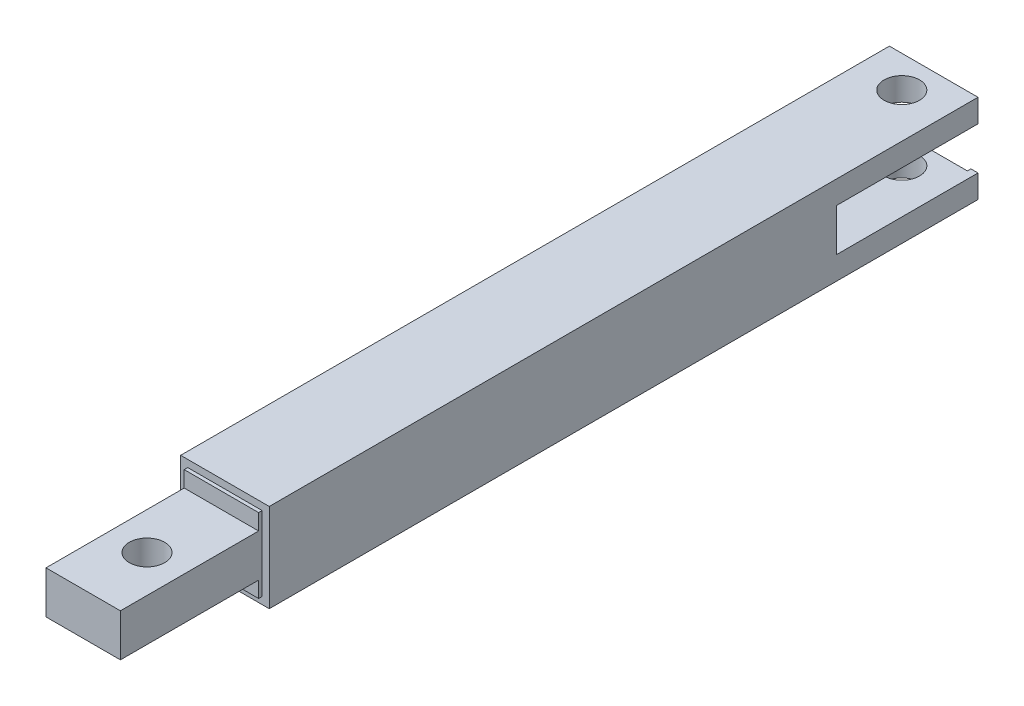
SolidWorks part; units mm, degrees
ref_plane "Front Plane" through (0, 0, 0) normal (0, 0, 1) x (1, 0, 0)
ref_plane "Top Plane" through (0, 0, 0) normal (0, 1, 0) x (1, 0, 0)
ref_plane "Right Plane" through (0, 0, 0) normal (1, 0, 0) x (0, 0, -1)
sketch "Sketch1" plane through (0, 0, 0) normal (0, 0, 1) x (1, 0, 0)
  line L0 (-10.5, 10.5) -> (10.5, 10.5)
  line L1 (-12.5, 12.5) -> (12.5, 12.5)
  line L2 (-12.5, 12.5) -> (-12.5, -12.5)
  line L3 (-12.5, -12.5) -> (12.5, -12.5)
  line L4 (12.5, 12.5) -> (12.5, -12.5)
  line L5 (-12.5, 12.5) -> (12.5, -12.5) construction
  line L6 (-12.5, -12.5) -> (12.5, 12.5) construction
  line L7 (10.5, 10.5) -> (10.5, -10.5)
  line L8 (-10.5, -10.5) -> (10.5, -10.5)
  line L9 (-10.5, 10.5) -> (-10.5, -10.5)
  point P0 (0, 0)
  dimension "D1" = 25
  dimension "D2" = 25
  dimension "D3" = 2
extrude "Boss-Extrude1" add sketch "Sketch1" along normal blind 200
sketch "Sketch2" plane through (12.5, 0, 0) normal (1, 0, 0) x (0, 0, -1)
  line L0 (0, -12.5) -> (0, 12.5) construction
  line L1 (0, -6) -> (-40, -6)
  line L2 (0, -6) -> (0, 6)
  line L3 (0, 6) -> (-40, 6)
  line L4 (-40, -6) -> (-40, 6)
  line L5 (-200, -12.5) -> (0, -12.5) construction
  dimension "D1" = 40
  dimension "D2" = 6.5
  dimension "D3" = 12
extrude "Cut-Extrude1" cut sketch "Sketch2" against normal through all
sketch "Sketch3" plane through (0, 12.5, 0) normal (0, 1, 0) x (1, 0, 0)
  line L0 (12.5, 0) -> (-12.5, 0) construction
  circle A0 centre (0, -9) radius 5
  dimension "D1" = 10
  dimension "D2" = 4
extrude "Cut-Extrude2" cut sketch "Sketch3" against normal through all
ref_plane "Plane1" through (0, 0, 240) normal (0, 0, 1) x (1, 0, 0)
sketch "Sketch5" plane through (0, 0, 240) normal (0, 0, 1) x (1, 0, 0)
  line L0 (-10.5, 10.5) -> (10.5, 10.5)
  line L1 (10.5, 10.5) -> (10.5, -10.5)
  line L2 (10.5, -10.5) -> (-10.5, -10.5)
  line L3 (-10.5, -10.5) -> (-10.5, 10.5)
extrude "Boss-Extrude2" add sketch "Sketch5" against normal blind 199 and the other way blind 1 from surface starting at face at (0, 0, 200)
extrude "Cut-Extrude4" cut sketch "Sketch3<2>" against normal blind 239
sketch "Sketch3<2>" plane through (0, 12.5, 0) normal (0, 1, 0) x (1, 0, 0) same geometry as "Sketch3"
sketch "Sketch6" plane through (0, 0, 1) normal (0, 0, -1) x (-1, 0, 0)
  line L1 (-10.5, 6) -> (10.5, 6)
  line L2 (-10.5, 6) -> (-10.5, -6)
  line L3 (-10.5, -6) -> (10.5, -6)
  line L4 (10.5, 6) -> (10.5, -6)
extrude "Cut-Extrude5" cut sketch "Sketch6" against normal up to surface (39 mm away) up to face at (11.5, 0, 40)
sketch "Sketch8" plane through (0, 0, 200) normal (0, 0, 1) x (1, 0, 0)
  line L0 (-10.5, 10.5) -> (-10.5, -10.5) construction
  line L1 (-10.5, 6) -> (10.5, 6)
  line L2 (-10.5, 6) -> (-10.5, -6)
  line L3 (-10.5, -6) -> (10.5, -6)
  line L4 (10.5, 6) -> (10.5, -6)
  line L5 (10.5, -10.5) -> (10.5, 10.5) construction
  line L6 (10.5, 10.5) -> (-10.5, 10.5) construction
  dimension "D1" = 12
  dimension "D2" = 4.5
extrude "Boss-Extrude3" add sketch "Sketch8" along normal blind 40
sketch "Sketch9" plane through (0, 6, 0) normal (0, 1, 0) x (1, 0, 0)
  line L0 (-26.7694, -240) -> (26.7694, -240) construction
  circle A0 centre (0, -222) radius 5
  dimension "D1" = 10
  dimension "D2" = 13
extrude "Cut-Extrude6" cut sketch "Sketch9" against normal through all
